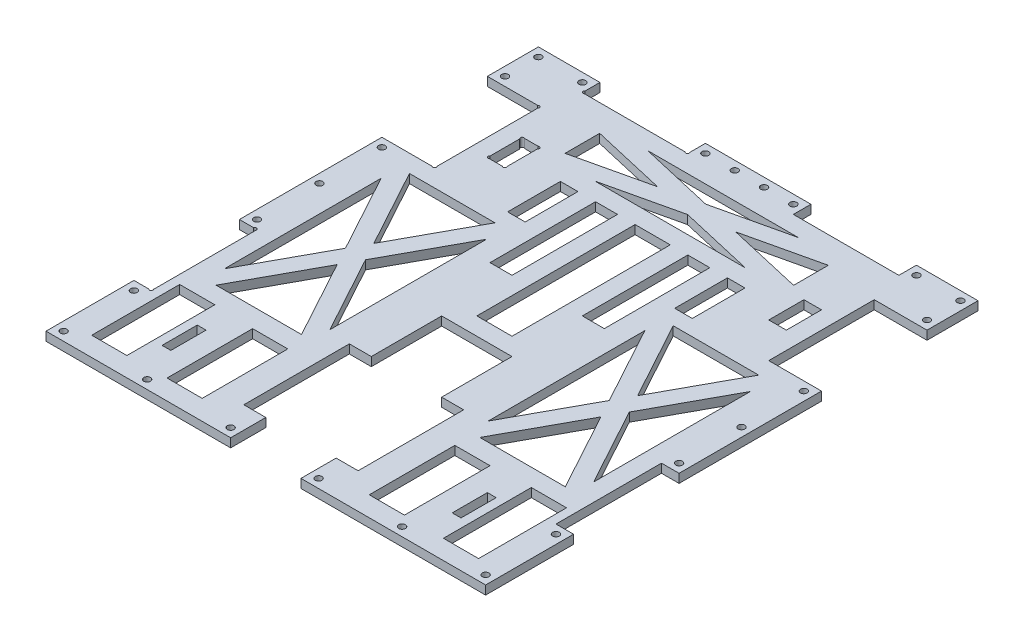
SolidWorks part; units mm, degrees
material "7050-T73510"
ref_plane "Front Plane" through (0, 0, 0) normal (0, 0, 1) x (1, 0, 0)
ref_plane "Top Plane" through (0, 0, 0) normal (0, 1, 0) x (1, 0, 0)
ref_plane "Right Plane" through (0, 0, 0) normal (1, 0, 0) x (0, 0, -1)
sketch "Sketch1" plane through (0, 0, 0) normal (0, 1, 0) x (1, 0, 0)
  line L1 (-158.75, -177.8) -> (158.75, -177.8)
  line L2 (-158.75, -177.8) -> (-158.75, 177.8)
  line L3 (-158.75, 177.8) -> (158.75, 177.8)
  line L4 (158.75, -177.8) -> (158.75, 177.8)
  line L5 (-158.75, -177.8) -> (158.75, 177.8) construction
  line L6 (-158.75, 177.8) -> (158.75, -177.8) construction
  point P0 (0, 0)
  dimension "D1" = 355.6
  dimension "D2" = 317.5
extrude "Boss-Extrude1" add sketch "Sketch1" along normal blind 6.35
sketch "Sketch2" plane through (0, 6.35, 0) normal (0, 1, 0) x (1, 0, 0)
  line L0 (-158.75, -177.8) -> (158.75, -177.8) construction
  line L1 (-25.4, -25.4) -> (25.4, -25.4)
  line L2 (-25.4, -25.4) -> (-25.4, -177.8)
  line L3 (-25.4, -177.8) -> (25.4, -177.8)
  line L4 (25.4, -25.4) -> (25.4, -177.8)
  line L5 (-25.4, -25.4) -> (25.4, -177.8) construction
  line L6 (-25.4, -177.8) -> (25.4, -25.4) construction
  point P0 (0, -101.6)
  dimension "D1" = 152.4
  dimension "D2" = 50.8
extrude "Cut-Extrude1" cut sketch "Sketch2" against normal through all
sketch "Sketch3" plane through (0, 6.35, 0) normal (0, 1, 0) x (1, 0, 0)
  line L0 (158.75, -177.8) -> (158.75, 177.8) construction
  line L5 (146.05, 140.97) -> (120.65, 140.97)
  line L11 (146.05, 140.97) -> (146.05, 64.77)
  line L13 (146.05, 64.77) -> (120.65, 64.77)
  line L15 (120.65, 140.97) -> (120.65, 64.77)
  line L16 (158.75, 177.8) -> (-158.75, 177.8) construction
  line L17 (107.95, 90.17) -> (95.25, 90.17)
  line L18 (107.95, 90.17) -> (107.95, 115.57)
  line L19 (107.95, 115.57) -> (95.25, 115.57)
  line L20 (95.25, 90.17) -> (95.25, 115.57)
  line L21 (0, -3.4925) -> (0, 3.4925) construction
  line L22 (-95.25, 90.17) -> (-95.25, 115.57)
  line L23 (-107.95, 115.57) -> (-95.25, 115.57)
  line L24 (-107.95, 90.17) -> (-107.95, 115.57)
  line L25 (-107.95, 90.17) -> (-95.25, 90.17)
  line L26 (-120.65, 140.97) -> (-120.65, 64.77)
  line L27 (-146.05, 64.77) -> (-120.65, 64.77)
  line L28 (-146.05, 140.97) -> (-146.05, 64.77)
  line L29 (-146.05, 140.97) -> (-120.65, 140.97)
  point P14 (107.95, 102.87)
  point P15 (120.65, 102.87)
  dimension "D1" = 25.4
  dimension "D2" = 12.7
  dimension "D3" = 12.7
  dimension "D4" = 12.7
  dimension "D5" = 25.4
  dimension "D6" = 76.2
  dimension "D7" = 36.83
extrude "Cut-Extrude2" cut sketch "Sketch3" against normal through all contours L5 L15 L13 L11 | L20 L17 L18 L19 | L29 L28 L27 L26 | L24 L25 L22 L23 | L26 L27 L28 L29 region at (133.35, 6.35, -102.87) region at (101.6, 6.35, -102.87) region at (-101.6, 6.35, -102.87) region at (-133.35, 6.35, -102.87)
sketch "Sketch4" plane through (0, 6.35, 0) normal (0, 1, 0) x (1, 0, 0)
  line L0 (-158.75, 177.8) -> (-158.75, -177.8) construction
  line L1 (-158.75, 140.97) -> (-146.05, 140.97)
  line L2 (-158.75, 140.97) -> (-158.75, 64.77)
  line L3 (-158.75, 64.77) -> (-146.05, 64.77)
  line L4 (-146.05, 140.97) -> (-146.05, 64.77)
  line L5 (0, -3.4925) -> (0, 3.4925) construction
  line L6 (-158.75, -114.3) -> (-146.05, -114.3)
  line L7 (-158.75, -114.3) -> (-158.75, -38.1)
  line L8 (-158.75, -38.1) -> (-146.05, -38.1)
  line L9 (-146.05, -114.3) -> (-146.05, -38.1)
  line L10 (158.75, 64.77) -> (146.05, 64.77)
  line L11 (146.05, 140.97) -> (146.05, 64.77)
  line L12 (158.75, 140.97) -> (146.05, 140.97)
  line L13 (158.75, 140.97) -> (158.75, 64.77)
  line L14 (158.75, -38.1) -> (146.05, -38.1)
  line L15 (146.05, -114.3) -> (146.05, -38.1)
  line L16 (158.75, -114.3) -> (146.05, -114.3)
  line L17 (158.75, -114.3) -> (158.75, -38.1)
  line L18 (158.75, 177.8) -> (-158.75, 177.8) construction
  line L19 (114.3, 165.1) -> (38.1, 165.1)
  line L20 (-114.3, 177.8) -> (-38.1, 177.8)
  line L21 (-114.3, 177.8) -> (-114.3, 165.1)
  line L22 (-114.3, 165.1) -> (-38.1, 165.1)
  line L23 (-38.1, 177.8) -> (-38.1, 165.1)
  line L24 (38.1, 177.8) -> (38.1, 165.1)
  line L25 (114.3, 177.8) -> (38.1, 177.8)
  line L26 (114.3, 177.8) -> (114.3, 165.1)
  line L27 (-25.4, -25.4) -> (-25.4, -177.8) construction
  line L28 (-25.4, -152.4) -> (-41.275, -152.4)
  line L29 (-25.4, -152.4) -> (-25.4, -76.2)
  line L30 (-25.4, -76.2) -> (-41.275, -76.2)
  line L31 (-41.275, -152.4) -> (-41.275, -76.2)
  line L32 (-158.75, -177.8) -> (-25.4, -177.8) construction
  line L33 (25.4, 101.6) -> (41.275, 101.6)
  line L34 (-25.4, 25.4) -> (-41.275, 25.4)
  line L35 (-25.4, 25.4) -> (-25.4, 101.6)
  line L36 (-25.4, 101.6) -> (-41.275, 101.6)
  line L37 (-41.275, 25.4) -> (-41.275, 101.6)
  line L38 (41.275, 25.4) -> (41.275, 101.6)
  line L39 (25.4, 25.4) -> (41.275, 25.4)
  line L40 (25.4, 25.4) -> (25.4, 101.6)
  line L41 (25.4, -76.2) -> (41.275, -76.2)
  line L42 (41.275, -152.4) -> (41.275, -76.2)
  line L43 (25.4, -152.4) -> (41.275, -152.4)
  line L44 (25.4, -152.4) -> (25.4, -76.2)
  dimension "D1" = 12.7
  dimension "D2" = 12.7
  dimension "D3" = 76.2
  dimension "D4" = 76.2
  dimension "D5" = 36.83
  dimension "D6" = 215.9
  dimension "D7" = 12.7
  dimension "D8" = 76.2
  dimension "D9" = 76.2
  dimension "D10" = 15.875
  dimension "D11" = 76.2
  dimension "D12" = 25.4
  dimension "D13" = 76.2
  dimension "D14" = 15.875
  dimension "D15" = 203.2
  dimension "D16" = 50.8
extrude "Cut-Extrude3" cut sketch "Sketch4" against normal through all
sketch "Sketch5" plane through (0, 6.35, 0) normal (0, 1, 0) x (1, 0, 0)
  line L0 (-41.275, -76.2) -> (-41.275, -152.4) construction
  line L5 (-41.275, 101.6) -> (-41.275, 25.4) construction
  line L6 (-85.725, -101.6) -> (-60.325, -101.6)
  line L7 (-133.35, -87.63) -> (-57.15, -87.63)
  line L8 (-133.35, -87.63) -> (-133.35, 52.07)
  line L9 (-133.35, 52.07) -> (-57.15, 52.07)
  line L10 (-57.15, -87.63) -> (-57.15, 52.07)
  line L11 (-133.35, -87.63) -> (-57.15, 52.07) construction
  line L12 (-133.35, 52.07) -> (-57.15, -87.63) construction
  line L13 (-82.55, 114.3) -> (82.55, 114.3)
  line L14 (-82.55, 114.3) -> (-82.55, 152.4)
  line L15 (-82.55, 152.4) -> (82.55, 152.4)
  line L16 (82.55, 114.3) -> (82.55, 152.4)
  line L17 (-82.55, 114.3) -> (82.55, 152.4) construction
  line L18 (-82.55, 152.4) -> (82.55, 114.3) construction
  line L23 (0, -3.4925) -> (0, 3.4925) construction
  line L24 (-12.7, -12.7) -> (12.7, -12.7)
  line L25 (-146.05, -114.3) -> (-146.05, -38.1) construction
  line L26 (-53.975, 101.6) -> (-66.675, 101.6)
  line L27 (-53.975, 101.6) -> (-53.975, 63.5)
  line L28 (-158.75, 64.77) -> (-158.75, -38.1) construction
  line L29 (-158.75, 64.77) -> (-120.65, 64.77) construction
  line L30 (-85.725, -101.6) -> (-85.725, -163.4194)
  line L31 (-12.7, -12.7) -> (-12.7, 101.6)
  line L32 (-12.7, 101.6) -> (12.7, 101.6)
  line L33 (12.7, -12.7) -> (12.7, 101.6)
  line L34 (-53.975, 63.5) -> (-66.675, 63.5)
  line L35 (-66.675, 101.6) -> (-66.675, 63.5)
  line L36 (53.975, 63.5) -> (66.675, 63.5)
  line L37 (-25.4, 25.4) -> (-25.4, 101.6) construction
  line L38 (-25.4, 101.6) -> (-41.275, 101.6) construction
  line L39 (-95.25, 90.17) -> (-95.25, 115.57) construction
  line L40 (-114.3, 165.1) -> (-38.1, 165.1) construction
  line L41 (-85.725, -163.4194) -> (-60.325, -163.4194)
  line L42 (-60.325, -101.6) -> (-60.325, -163.4194)
  line L43 (-138.9246, 49.0293) -> (-62.7246, -90.6707)
  line L44 (-127.7754, -90.6707) -> (-51.5754, 49.0293)
  line L45 (66.675, 101.6) -> (66.675, 63.5)
  line L46 (53.975, 101.6) -> (66.675, 101.6)
  line L47 (-83.9779, 146.2126) -> (81.1221, 108.1126)
  line L48 (-81.1221, 108.1126) -> (83.9779, 146.2126)
  line L49 (53.975, 101.6) -> (53.975, 63.5)
  line L51 (-127.7754, 55.1107) -> (-51.5754, -84.5893)
  line L52 (-138.9246, -84.5893) -> (-62.7246, 55.1107)
  line L55 (-81.1221, 158.5874) -> (83.9779, 120.4874)
  line L56 (-83.9779, 120.4874) -> (81.1221, 158.5874)
  line L57 (-139.7, -100.33) -> (-114.3, -100.33)
  line L58 (-139.7, -100.33) -> (-139.7, -163.83)
  line L59 (-139.7, -163.83) -> (-114.3, -163.83)
  line L60 (-114.3, -100.33) -> (-114.3, -163.83)
  line L63 (-107.95, -144.78) -> (-101.6, -144.78)
  line L64 (-107.95, -144.78) -> (-107.95, -119.38)
  line L65 (-107.95, -119.38) -> (-101.6, -119.38)
  line L66 (-101.6, -144.78) -> (-101.6, -119.38)
  line L67 (-107.95, -144.78) -> (-101.6, -119.38) construction
  line L68 (-107.95, -119.38) -> (-101.6, -144.78) construction
  point P5 (-95.25, -17.78)
  point P10 (0, 133.35)
  point P15 (0, 44.45)
  point P34 (-104.775, -132.08)
  point P45 (-33.3375, 101.6)
  point P87 (-114.3, -132.08)
  dimension "D3" = 12.7
  dimension "D4" = 19.05
  dimension "D5" = 139.7
  dimension "D6" = 25.4
  dimension "D7" = 12.7
  dimension "D8" = 76.2
  dimension "D9" = 25.4
  dimension "D10" = 12.7
  dimension "D11" = 165.1
  dimension "D12" = 12.7
  dimension "D13" = 12.7
  dimension "D14" = 12.7
  dimension "D17" = 25.4
  dimension "D18" = 63.5
  dimension "D19" = 12.7
  dimension "D20" = 6.35
  dimension "D21" = 38.1
  dimension "D22" = 38.1
  dimension "D23" = 25.4
  dimension "D15" = 114.3
  dimension "D16" = 12.7
extrude "Cut-Extrude4" cut sketch "Sketch5" against normal through all contours L44 L7 L43 | L8 L52 L43 | L51 L52 L9 | L44 L51 L10 | L33 | L32 | L31 | L24 | L48 L13 L47 | L48 L55 L16 | L55 L56 L15 | L14 L56 L47 | L60 L57 L58 L59 | L63 L66 L65 L64 | L42 L6 L30 L41 | L26 L35 L34 L27 | L46 L49 L36 L45 region at (-73.025, 6.35, 132.5097) region at (-95.25, 6.35, 68.767) region at (-123.0611, 6.35, 17.78) region at (-67.4389, 6.35, 17.78) region at (-95.25, 6.35, -33.207) region at (0, 6.35, -118.4777) region at (-64.4466, 6.35, -133.35) region at (64.4466, 6.35, -133.35) region at (0, 6.35, -148.2223) region at (0, 6.35, -44.45) region at (-60.325, 6.35, -82.55) region at (60.325, 6.35, -82.55) region at (-127, 6.35, 132.08) region at (-104.775, 6.35, 132.08)
mirror "Mirror1" about plane through (0, 0, 0) normal (1, 0, 0) of "Cut-Extrude4"
sketch "Sketch7" plane through (0, 6.35, 0) normal (0, 1, 0) x (1, 0, 0)
  line L0 (-158.75, -177.8) -> (-25.4, -177.8) construction
  line L1 (-158.75, -114.3) -> (-158.75, -177.8) construction
  line L2 (0, -3.4925) -> (0, 3.4925) construction
  line L3 (-158.75, 177.8) -> (-158.75, 140.97) construction
  line L4 (-114.3, 177.8) -> (-158.75, 177.8) construction
  line L6 (38.1, 177.8) -> (-38.1, 177.8) construction
  line L7 (-38.1, 165.1) -> (-38.1, 177.8) construction
  line L8 (-25.4, -152.4) -> (-25.4, -177.8) construction
  line L9 (-158.75, -114.3) -> (-146.05, -114.3) construction
  line L10 (-158.75, 64.77) -> (-158.75, -38.1) construction
  line L11 (-146.05, -38.1) -> (-158.75, -38.1) construction
  line L12 (-158.75, 64.77) -> (-120.65, 64.77) construction
  circle A0 centre (-152.4, -171.45) radius 2.413
  circle A14 centre (-152.4, 171.45) radius 2.413
  circle A15 centre (-120.65, 171.45) radius 2.413
  circle A16 centre (-152.4, 147.32) radius 2.413
  circle A34 centre (-31.75, 171.45) radius 2.413
  circle A35 centre (-10.5833, 171.45) radius 2.413
  circle A36 centre (10.5833, 171.45) radius 2.413
  circle A37 centre (31.75, 171.45) radius 2.413
  circle A38 centre (-31.75, -171.45) radius 2.413
  circle A39 centre (-92.075, -171.45) radius 2.413
  circle A40 centre (-152.4, -120.65) radius 2.413
  circle A41 centre (-152.4, -31.75) radius 2.413
  circle A42 centre (-152.4, 58.42) radius 2.413
  circle A43 centre (-152.4, 13.335) radius 2.413
  circle A44 centre (31.75, -171.45) radius 2.413
  circle A45 centre (152.4, 13.335) radius 2.413
  circle A46 centre (152.4, 58.42) radius 2.413
  circle A47 centre (152.4, -31.75) radius 2.413
  circle A48 centre (152.4, -120.65) radius 2.413
  circle A49 centre (92.075, -171.45) radius 2.413
  circle A50 centre (152.4, 147.32) radius 2.413
  circle A51 centre (120.65, 171.45) radius 2.413
  circle A52 centre (152.4, 171.45) radius 2.413
  circle A53 centre (152.4, -171.45) radius 2.413
  dimension "D1" = 4.826
  dimension "D6" = 6.35
  dimension "D9" = 4.826
  dimension "D14" = 4.826
  dimension "D4" = 4.826
  dimension "D5" = 4.826
  dimension "D8" = 4.826
  dimension "D20" = 4.826
  dimension "D24" = 4.826
  dimension "D25" = 4.826
  dimension "D2" = 6.35
  dimension "D3" = 6.35
  dimension "D7" = 60.325
  dimension "D10" = 6.35
  dimension "D11" = 6.35
  dimension "D15" = 6.35
  dimension "D16" = 6.35
  dimension "D18" = 6.35
  dimension "D19" = 6.35
  dimension "D21" = 6.35
  dimension "D22" = 6.35
  dimension "D23" = 6.35
  dimension "D26" = 45.085
  dimension "D12" = 2
  dimension "D13" = 2
  dimension "D17" = 4
extrude "Cut-Extrude6" cut sketch "Sketch7" against normal through all
sketch "Sketch8" plane through (0, 6.35, 0) normal (0, 1, 0) x (1, 0, 0)
  circle A0 centre (-39.0994, 165.8837) radius 1.27
  circle A1 centre (-113.5398, 166.1174) radius 1.27
  circle A2 centre (-121.56, 140.0841) radius 1.27
  circle A3 centre (-121.5656, 65.6501) radius 1.27
  circle A4 centre (-147.253, -38.507) radius 1.27
  circle A5 centre (-147.0444, -113.51) radius 1.27
  circle A6 centre (-107.1943, 114.5493) radius 1.27
  circle A7 centre (-96.0341, 114.5709) radius 1.27
  circle A8 centre (-107.1845, 91.1833) radius 1.27
  circle A10 centre (-96.2084, 91.0033) radius 1.27
extrude "Cut-Extrude7" cut sketch "Sketch8" against normal through all
